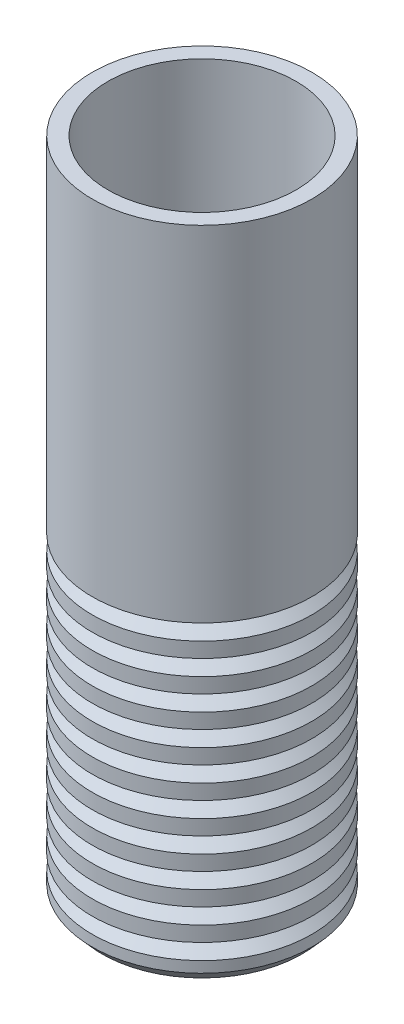
SolidWorks part; units mm, degrees
material "6061-T4 (SS)"
ref_plane "Front Plane" through (0, 0, 0) normal (0, 0, 1) x (1, 0, 0)
ref_plane "Top Plane" through (0, 0, 0) normal (0, 1, 0) x (1, 0, 0)
ref_plane "Right Plane" through (0, 0, 0) normal (1, 0, 0) x (0, 0, -1)
sketch "Sketch2" plane through (0, 0, 0) normal (0, 0, 1) x (1, 0, 0)
  line L0 (0, 0) -> (0, 21) construction
  line L1 (-3, 21) -> (-3, 11)
  line L2 (-3, 21) -> (-3.5022, 21)
  line L3 (-3.5022, 21) -> (-3.5022, 10.02)
  line L4 (-3, 11) -> (-1.25, 10.2)
  line L5 (-1.25, 10.2) -> (-1.25, 0)
  line L6 (-1.25, 0) -> (-3.19, 0)
  line L7 (-3.19, 0) -> (-3.5022, 0.35)
  line L8 (-3.5022, 0.35) -> (-3.5022, 0.7)
  line L9 (-3.5022, 0.7) -> (-2.9416, 1.2)
  line L10 (-2.9416, 1.2) -> (-3.5022, 1.2)
  line L11 (-3.5022, 1.2) -> (-3.5022, 1.68)
  line L12 (-2.9416, 2.18) -> (-3.5022, 2.18)
  line L13 (-3.5022, 2.18) -> (-3.5022, 2.66)
  line L14 (-3.5022, 1.68) -> (-2.9416, 2.18)
  line L15 (-3.5022, 2.66) -> (-2.9416, 3.16)
  line L16 (-3.5022, 3.16) -> (-3.5022, 3.64)
  line L17 (-2.9416, 3.16) -> (-3.5022, 3.16)
  line L18 (-2.9416, 4.14) -> (-3.5022, 4.14)
  line L19 (-3.5022, 4.14) -> (-3.5022, 4.62)
  line L20 (-3.5022, 3.64) -> (-2.9416, 4.14)
  line L21 (-2.9416, 7.08) -> (-3.5022, 7.08)
  line L22 (-3.5022, 7.56) -> (-2.9416, 8.06)
  line L23 (-3.5022, 4.62) -> (-2.9416, 5.12)
  line L24 (-3.5022, 5.6) -> (-2.9416, 6.1)
  line L25 (-3.5022, 5.12) -> (-3.5022, 5.6)
  line L26 (-2.9416, 5.12) -> (-3.5022, 5.12)
  line L27 (-3.5022, 6.58) -> (-2.9416, 7.08)
  line L28 (-2.9416, 6.1) -> (-3.5022, 6.1)
  line L29 (-2.9416, 8.06) -> (-3.5022, 8.06)
  line L30 (-3.5022, 7.08) -> (-3.5022, 7.56)
  line L31 (-3.5022, 8.06) -> (-3.5022, 8.54)
  line L32 (-3.5022, 6.1) -> (-3.5022, 6.58)
  line L33 (-2.9416, 9.04) -> (-3.5022, 9.04)
  line L34 (-2.9416, 10.02) -> (-3.5022, 10.02)
  line L35 (-3.5022, 9.52) -> (-2.9416, 10.02)
  line L36 (-3.5022, 8.54) -> (-2.9416, 9.04)
  line L38 (-3.5022, 9.04) -> (-3.5022, 9.52)
  dimension "D1" = 21
  dimension "D2" = 3
  dimension "D3" = 10
  dimension "D4" = 0.5022
  dimension "D5" = 10.98
  dimension "D6" = 10.2
  dimension "D7" = 0.8
  dimension "D8" = 1.25
  dimension "D9" = 1.94
  dimension "D10" = 0.35
  dimension "D11" = 0.35
  dimension "D12" = 0.48
  dimension "D13" = 0.48
  dimension "D14" = 0.5
  dimension "D15" = 0.5
  dimension "D16" = 0.48
  dimension "D17" = 0.5
  dimension "D18" = 0.48
  dimension "D19" = 0.5
  dimension "D20" = 0.48
  dimension "D21" = 0.5
revolve "Revolve1" add sketch "Sketch2" angle 360 about L0
